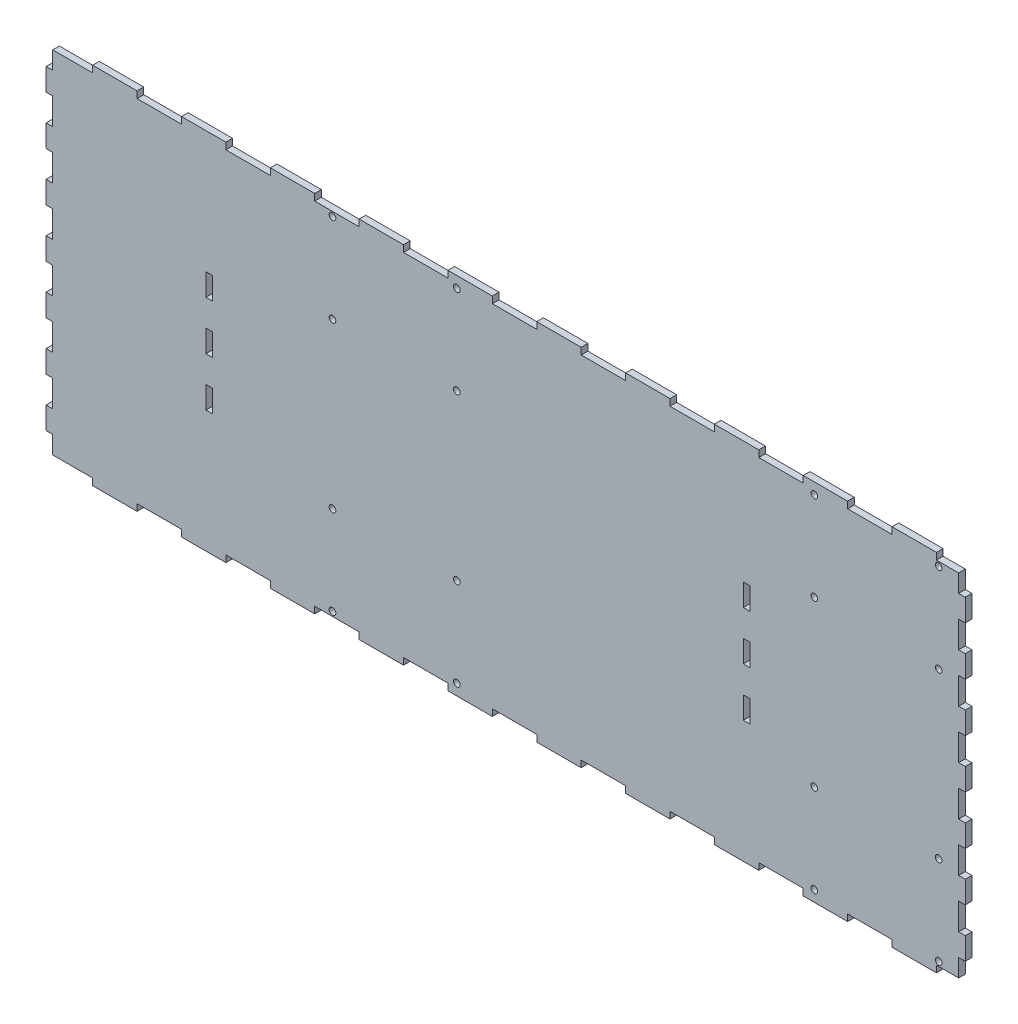
SolidWorks part; units mm, degrees
material "birch 3mm plywood"
ref_plane "Front Plane" through (0, 0, 0) normal (0, 0, 1) x (1, 0, 0)
ref_plane "Top Plane" through (0, 0, 0) normal (0, 1, 0) x (1, 0, 0)
ref_plane "Right Plane" through (0, 0, 0) normal (1, 0, 0) x (0, 0, -1)
sketch "Sketch1" plane through (0, 0, 152) normal (0, 0, 1) x (1, 0, 0)
  line L1 (-207, 82) -> (207, 82)
  line L2 (-207, 82) -> (-207, -82)
  line L3 (-207, -82) -> (207, -82)
  line L4 (207, 82) -> (207, -82)
  line L12 (200, -75) -> (-200, -75) construction
  line L13 (200, 75) -> (200, -75) construction
  line L14 (-200, -75) -> (-200, 75) construction
  line L15 (-200, 75) -> (200, 75) construction
  line L26 (-200, 0) -> (200, 0) construction
  line L31 (-200, 0) -> (200, 0) construction
  point P14 (0, 0)
  point P15 (0, 0)
  point P32 (-47.5, -25.9413)
  point P35 (256.981, -145.9413)
  point P38 (10.8894, 25.9413)
  point P51 (10.8894, -25.9413)
  point P54 (256.981, 145.9413)
  dimension "D1" = 7
  dimension "D2" = 7
  dimension "D3" = 7
  dimension "D4" = 7
  dimension "D5" = 150
  dimension "D6" = 400
extrude "Boss-Extrude1" add sketch "Sketch1" along normal blind 3
sketch "Sketch2" plane through (-207, 0, 0) normal (-1, 0, 0) x (0, 0, 1)
  line L7 (155, -82) -> (152, -82)
  line L8 (152, -82) -> (152, -71)
  line L9 (152, 82) -> (155, 82)
  line L10 (155, 82) -> (155, 71)
  line L11 (152, -61) -> (152, -49)
  line L12 (155, -71) -> (155, -82)
  line L13 (155, -49) -> (155, -61)
  line L14 (152, -39) -> (152, -27)
  line L15 (152, -17) -> (152, -5)
  line L16 (155, -27) -> (155, -39)
  line L17 (155, -5) -> (155, -17)
  line L18 (152, 5) -> (152, 17)
  line L19 (152, 27) -> (152, 39)
  line L20 (155, 17) -> (155, 5)
  line L21 (155, 39) -> (155, 27)
  line L22 (152, 49) -> (152, 61)
  line L23 (152, 71) -> (152, 82)
  line L24 (155, 61) -> (155, 49)
  line L76 (132.5, 88.6) -> (132.5, 93.6)
  line L77 (132.5, 88.6) -> (132.5, 93.6)
  line L78 (129.5, 98.6) -> (128.8771, 98.6)
  line L79 (129.5, 98.6) -> (128.8771, 98.6)
  line L80 (129.5, 82) -> (129.5, 88.6)
  line L81 (129.5, 82) -> (129.5, 88.6)
  line L82 (129.5, 88.6) -> (132.5, 88.6)
  line L83 (129.5, 88.6) -> (132.5, 88.6)
  line L85 (16, 82) -> (16, -82)
  line L102 (129.5, -82) -> (133, -82)
  line L103 (133, -82) -> (133, -79)
  line L104 (133, -79) -> (145, -79)
  line L105 (145, -79) -> (145, -82)
  line L106 (145, -82) -> (155, -82)
  line L107 (155, -82) -> (155, -71)
  line L108 (155, -71) -> (152, -71)
  line L109 (152, -71) -> (152, -61)
  line L110 (152, -61) -> (155, -61)
  line L111 (155, -61) -> (155, -49)
  line L112 (155, -49) -> (152, -49)
  line L113 (152, -49) -> (152, -39)
  line L114 (152, -39) -> (155, -39)
  line L115 (155, -39) -> (155, -27)
  line L116 (155, -27) -> (152, -27)
  line L117 (152, -27) -> (152, -17)
  line L118 (152, -17) -> (155, -17)
  line L119 (155, -17) -> (155, -5)
  line L120 (155, -5) -> (152, -5)
  line L121 (152, -5) -> (152, 5)
  line L122 (152, 5) -> (155, 5)
  line L123 (155, 5) -> (155, 17)
  line L124 (155, 17) -> (152, 17)
  line L125 (152, 17) -> (152, 27)
  line L126 (152, 27) -> (155, 27)
  line L127 (155, 27) -> (155, 39)
  line L128 (155, 39) -> (152, 39)
  line L129 (152, 39) -> (152, 49)
  line L130 (152, 49) -> (155, 49)
  line L131 (155, 49) -> (155, 61)
  line L132 (155, 61) -> (152, 61)
  line L133 (152, 61) -> (152, 71)
  line L134 (152, 71) -> (155, 71)
  line L135 (155, 71) -> (155, 82)
  line L136 (155, 82) -> (145, 82)
  line L137 (145, 82) -> (145, 79)
  line L138 (145, 79) -> (133, 79)
  line L139 (133, 79) -> (133, 82)
  line L140 (133, 82) -> (129.5, 82)
  line L184 (155, -71) -> (152, -71)
  line L186 (152, -61) -> (155, -61)
  line L188 (155, -49) -> (152, -49)
  line L190 (152, -39) -> (155, -39)
  line L192 (155, -27) -> (152, -27)
  line L194 (152, -17) -> (155, -17)
  line L196 (155, -5) -> (152, -5)
  line L198 (152, 5) -> (155, 5)
  line L200 (155, 17) -> (152, 17)
  line L202 (152, 27) -> (155, 27)
  line L204 (155, 39) -> (152, 39)
  line L206 (152, 49) -> (155, 49)
  line L208 (155, 61) -> (152, 61)
  line L210 (152, 71) -> (155, 71)
  line L297 (132.5, 93.6) -> (129.5, 93.6)
  line L298 (132.5, 93.6) -> (129.5, 93.6)
  line L299 (129.5, 93.6) -> (129.5, 98.6)
  line L300 (129.5, 93.6) -> (129.5, 98.6)
  line L301 (128.8771, -98.6) -> (129.5, -98.6)
  line L302 (128.8771, -98.6) -> (129.5, -98.6)
  line L303 (129.5, -98.6) -> (129.5, -93.6)
  line L304 (129.5, -98.6) -> (129.5, -93.6)
  line L305 (129.5, -93.6) -> (132.5, -93.6)
  line L306 (129.5, -93.6) -> (132.5, -93.6)
  line L307 (132.5, -93.6) -> (132.5, -88.6)
  line L308 (132.5, -93.6) -> (132.5, -88.6)
  line L309 (132.5, -88.6) -> (129.5, -88.6)
  line L310 (132.5, -88.6) -> (129.5, -88.6)
  line L311 (129.5, -88.6) -> (129.5, -82)
  line L312 (129.5, -88.6) -> (129.5, -82)
  arc A4 (128.8771, 98.6) -> (16, 82) centre (128.8771, -293.4723) ccw
  arc A5 (128.8771, 98.6) -> (16, 82) centre (128.8771, -293.4723) ccw
  arc A6 (16, -82) -> (128.8771, -98.6) centre (128.8771, 293.4723) ccw
  arc A7 (16, -82) -> (128.8771, -98.6) centre (128.8771, 293.4723) ccw
  line M77 (152, 82) -> (152, -82)
  line M78 (152, -82) -> (155, -82)
  line M79 (155, -82) -> (155, 82)
  line M80 (155, 82) -> (152, 82)
  dimension "D1" = 0
extrude "Cut-Extrude1" cut sketch "Sketch2" against normal blind 3 contours L184 M79 M77 M78 | L188 L186 M79 M77 | L192 L190 M79 M77 | L196 L194 M79 M77 | L200 L198 M79 M77 | L204 L202 M79 M77 | L208 L206 M79 M77 | L210 M77 M79 M80 region at (-207, -76.5, 153.5) region at (-207, -55, 153.5) region at (-207, -33, 153.5) region at (-207, -11, 153.5) region at (-207, 11, 153.5) region at (-207, 33, 153.5) region at (-207, 55, 153.5) region at (-207, 76.5, 153.5)
mirror "Mirror1" about plane through (0, 0, 0) normal (1, 0, 0) of "Cut-Extrude1"
sketch "Sketch3" plane through (0, 82, 0) normal (0, 1, 0) x (1, 0, 0)
  line L92 (174, -152) -> (194, -152)
  line L93 (194, -152) -> (194, -155)
  line L94 (194, -155) -> (204, -155)
  line L97 (207, -45) -> (204, -45)
  line L120 (204, -16) -> (-204, -16)
  line L123 (-204, -45) -> (-207, -45)
  line L146 (-204, -155) -> (-186, -155)
  line L147 (-186, -155) -> (-186, -152)
  line L148 (-186, -152) -> (-166, -152)
  line L149 (-166, -152) -> (-166, -155)
  line L150 (-166, -155) -> (-146, -155)
  line L151 (-146, -155) -> (-146, -152)
  line L152 (-146, -152) -> (-126, -152)
  line L153 (-126, -152) -> (-126, -155)
  line L154 (-126, -155) -> (-106, -155)
  line L155 (-106, -155) -> (-106, -152)
  line L156 (-106, -152) -> (-86, -152)
  line L157 (-86, -152) -> (-86, -155)
  line L158 (-86, -155) -> (-66, -155)
  line L159 (-66, -155) -> (-66, -152)
  line L160 (-66, -152) -> (-46, -152)
  line L161 (-46, -152) -> (-46, -155)
  line L162 (-46, -155) -> (-26, -155)
  line L163 (-26, -155) -> (-26, -152)
  line L164 (-26, -152) -> (-6, -152)
  line L165 (-6, -152) -> (-6, -155)
  line L166 (-6, -155) -> (14, -155)
  line L167 (14, -155) -> (14, -152)
  line L168 (14, -152) -> (34, -152)
  line L169 (34, -152) -> (34, -155)
  line L170 (34, -155) -> (54, -155)
  line L171 (54, -155) -> (54, -152)
  line L172 (54, -152) -> (74, -152)
  line L173 (74, -152) -> (74, -155)
  line L174 (74, -155) -> (94, -155)
  line L175 (94, -155) -> (94, -152)
  line L176 (94, -152) -> (114, -152)
  line L177 (114, -152) -> (114, -155)
  line L178 (114, -155) -> (134, -155)
  line L179 (134, -155) -> (134, -152)
  line L180 (134, -152) -> (154, -152)
  line L181 (154, -152) -> (154, -155)
  line L182 (154, -155) -> (174, -155)
  line L183 (174, -155) -> (174, -152)
  line L184 (174, -152) -> (194, -152)
  line L185 (194, -152) -> (194, -155)
  line L186 (194, -155) -> (204, -155)
  line L212 (204, -16) -> (-204, -16)
  line L238 (-204, -155) -> (-186, -155)
  line L239 (-186, -155) -> (-186, -152)
  line L240 (-186, -152) -> (-166, -152)
  line L241 (-166, -152) -> (-166, -155)
  line L242 (-166, -155) -> (-146, -155)
  line L243 (-146, -155) -> (-146, -152)
  line L244 (-146, -152) -> (-126, -152)
  line L245 (-126, -152) -> (-126, -155)
  line L246 (-126, -155) -> (-106, -155)
  line L247 (-106, -155) -> (-106, -152)
  line L248 (-106, -152) -> (-86, -152)
  line L249 (-86, -152) -> (-86, -155)
  line L250 (-86, -155) -> (-66, -155)
  line L251 (-66, -155) -> (-66, -152)
  line L252 (-66, -152) -> (-46, -152)
  line L253 (-46, -152) -> (-46, -155)
  line L254 (-46, -155) -> (-26, -155)
  line L255 (-26, -155) -> (-26, -152)
  line L256 (-26, -152) -> (-6, -152)
  line L257 (-6, -152) -> (-6, -155)
  line L258 (-6, -155) -> (14, -155)
  line L259 (14, -155) -> (14, -152)
  line L260 (14, -152) -> (34, -152)
  line L261 (34, -152) -> (34, -155)
  line L262 (34, -155) -> (54, -155)
  line L263 (54, -155) -> (54, -152)
  line L264 (54, -152) -> (74, -152)
  line L265 (74, -152) -> (74, -155)
  line L266 (74, -155) -> (94, -155)
  line L267 (94, -155) -> (94, -152)
  line L268 (94, -152) -> (114, -152)
  line L269 (114, -152) -> (114, -155)
  line L270 (114, -155) -> (134, -155)
  line L271 (134, -155) -> (134, -152)
  line L272 (134, -152) -> (154, -152)
  line L273 (154, -152) -> (154, -155)
  line L274 (154, -155) -> (174, -155)
  line L275 (174, -155) -> (174, -152)
  line L576 (-204, -45) -> (-207, -45)
  line L577 (-207, -45) -> (-207, -57)
  line L578 (-207, -45) -> (-207, -57)
  line L579 (-207, -57) -> (-204, -57)
  line L580 (-207, -57) -> (-204, -57)
  line L581 (-204, -57) -> (-204, -67)
  line L582 (-204, -57) -> (-204, -67)
  line L583 (-204, -67) -> (-207, -67)
  line L584 (-204, -67) -> (-207, -67)
  line L585 (-207, -67) -> (-207, -79)
  line L586 (-207, -67) -> (-207, -79)
  line L587 (-207, -79) -> (-204, -79)
  line L588 (-207, -79) -> (-204, -79)
  line L589 (-204, -79) -> (-204, -89)
  line L590 (-204, -79) -> (-204, -89)
  line L591 (-204, -89) -> (-207, -89)
  line L592 (-204, -89) -> (-207, -89)
  line L593 (-207, -89) -> (-207, -101)
  line L594 (-207, -89) -> (-207, -101)
  line L595 (-207, -101) -> (-204, -101)
  line L596 (-207, -101) -> (-204, -101)
  line L597 (-204, -101) -> (-204, -111)
  line L598 (-204, -101) -> (-204, -111)
  line L599 (-204, -111) -> (-207, -111)
  line L600 (-204, -111) -> (-207, -111)
  line L601 (-207, -111) -> (-207, -123)
  line L602 (-207, -111) -> (-207, -123)
  line L603 (-207, -123) -> (-204, -123)
  line L604 (-207, -123) -> (-204, -123)
  line L605 (-204, -123) -> (-204, -133)
  line L606 (-204, -123) -> (-204, -133)
  line L607 (-204, -133) -> (-207, -133)
  line L608 (-204, -133) -> (-207, -133)
  line L609 (-207, -133) -> (-207, -145)
  line L610 (-207, -133) -> (-207, -145)
  line L611 (-207, -145) -> (-204, -145)
  line L612 (-207, -145) -> (-204, -145)
  line L613 (-204, -145) -> (-204, -155)
  line L614 (-204, -145) -> (-204, -155)
  line L615 (-204, -16) -> (-204, -23)
  line L616 (-204, -16) -> (-204, -23)
  line L617 (-204, -23) -> (-207, -23)
  line L618 (-204, -23) -> (-207, -23)
  line L619 (-207, -23) -> (-207, -35)
  line L620 (-207, -23) -> (-207, -35)
  line L621 (-207, -35) -> (-204, -35)
  line L622 (-207, -35) -> (-204, -35)
  line L623 (-204, -35) -> (-204, -45)
  line L624 (-204, -35) -> (-204, -45)
  line L741 (207, -45) -> (204, -45)
  line L742 (204, -45) -> (204, -35)
  line L743 (204, -45) -> (204, -35)
  line L744 (204, -35) -> (207, -35)
  line L745 (204, -35) -> (207, -35)
  line L746 (207, -35) -> (207, -23)
  line L747 (207, -35) -> (207, -23)
  line L748 (207, -23) -> (204, -23)
  line L749 (207, -23) -> (204, -23)
  line L750 (204, -23) -> (204, -16)
  line L751 (204, -23) -> (204, -16)
  line L752 (204, -155) -> (204, -145)
  line L753 (204, -155) -> (204, -145)
  line L754 (204, -145) -> (207, -145)
  line L755 (204, -145) -> (207, -145)
  line L756 (207, -145) -> (207, -133)
  line L757 (207, -145) -> (207, -133)
  line L758 (207, -133) -> (204, -133)
  line L759 (207, -133) -> (204, -133)
  line L760 (204, -133) -> (204, -123)
  line L761 (204, -133) -> (204, -123)
  line L762 (204, -123) -> (207, -123)
  line L763 (204, -123) -> (207, -123)
  line L764 (207, -123) -> (207, -111)
  line L765 (207, -123) -> (207, -111)
  line L766 (207, -111) -> (204, -111)
  line L767 (207, -111) -> (204, -111)
  line L768 (204, -111) -> (204, -101)
  line L769 (204, -111) -> (204, -101)
  line L770 (204, -101) -> (207, -101)
  line L771 (204, -101) -> (207, -101)
  line L772 (207, -101) -> (207, -89)
  line L773 (207, -101) -> (207, -89)
  line L774 (207, -89) -> (204, -89)
  line L775 (207, -89) -> (204, -89)
  line L776 (204, -89) -> (204, -79)
  line L777 (204, -89) -> (204, -79)
  line L778 (204, -79) -> (207, -79)
  line L779 (204, -79) -> (207, -79)
  line L780 (207, -79) -> (207, -67)
  line L781 (207, -79) -> (207, -67)
  line L782 (207, -67) -> (204, -67)
  line L783 (207, -67) -> (204, -67)
  line L784 (204, -67) -> (204, -57)
  line L785 (204, -67) -> (204, -57)
  line L786 (204, -57) -> (207, -57)
  line L787 (204, -57) -> (207, -57)
  line L788 (207, -57) -> (207, -45)
  line L789 (207, -57) -> (207, -45)
  dimension "D1" = 0
extrude "Cut-Extrude2" cut sketch "Sketch3" against normal blind 3
mirror "Mirror2" about plane through (0, 0, 0) normal (0, 1, 0) of "Cut-Extrude2"
sketch "Sketch4" plane through (0, 0, 155) normal (0, 0, 1) x (1, 0, 0)
  line L0 (-132, 27) -> (-132, 17) construction
  line L1 (-132, 17) -> (-135, 17) construction
  line L2 (-135, 17) -> (-135, 27) construction
  line L3 (-135, 27) -> (-132, 27) construction
  line L4 (-132, 5) -> (-132, -5) construction
  line L5 (-132, -5) -> (-135, -5) construction
  line L6 (-135, -5) -> (-135, 5) construction
  line L7 (-135, 5) -> (-132, 5) construction
  line L8 (-132, -17) -> (-132, -27) construction
  line L9 (-132, -27) -> (-135, -27) construction
  line L10 (-135, -27) -> (-135, -17) construction
  line L11 (-135, -17) -> (-132, -17) construction
  line L12 (-132, 27) -> (-132, 17)
  line L13 (-132, 17) -> (-135, 17)
  line L14 (-135, 17) -> (-135, 27)
  line L15 (-135, 27) -> (-132, 27)
  line L16 (-132, 5) -> (-132, -5)
  line L17 (-132, -5) -> (-135, -5)
  line L18 (-135, -5) -> (-135, 5)
  line L19 (-135, 5) -> (-132, 5)
  line L20 (-132, -17) -> (-132, -27)
  line L21 (-132, -27) -> (-135, -27)
  line L22 (-135, -27) -> (-135, -17)
  line L23 (-135, -17) -> (-132, -17)
  line L24 (110, 27) -> (110, 17) construction
  line L25 (110, 17) -> (107, 17) construction
  line L26 (107, 17) -> (107, 27) construction
  line L27 (107, 27) -> (110, 27) construction
  line L28 (110, 5) -> (110, -5) construction
  line L29 (110, -5) -> (107, -5) construction
  line L30 (107, -5) -> (107, 5) construction
  line L31 (107, 5) -> (110, 5) construction
  line L32 (110, -17) -> (110, -27) construction
  line L33 (110, -27) -> (107, -27) construction
  line L34 (107, -27) -> (107, -17) construction
  line L35 (107, -17) -> (110, -17) construction
  line L36 (110, 27) -> (110, 17)
  line L37 (110, 17) -> (107, 17)
  line L38 (107, 17) -> (107, 27)
  line L39 (107, 27) -> (110, 27)
  line L40 (110, 5) -> (110, -5)
  line L41 (110, -5) -> (107, -5)
  line L42 (107, -5) -> (107, 5)
  line L43 (107, 5) -> (110, 5)
  line L44 (110, -17) -> (110, -27)
  line L45 (110, -27) -> (107, -27)
  line L46 (107, -27) -> (107, -17)
  line L47 (107, -17) -> (110, -17)
  line L80 (207, 0) -> (-207, 0) construction
  line L81 (207, -5) -> (207, 5) construction
  line L82 (-207, 5) -> (-207, -5) construction
  circle A0 centre (139, 37) radius 1.5 construction
  circle A1 centre (195, 37) radius 1.5 construction
  circle A2 centre (195, 77) radius 1.5 construction
  circle A3 centre (139, 77) radius 1.5 construction
  circle A4 centre (-78, 77) radius 1.5 construction
  circle A5 centre (-22, 77) radius 1.5 construction
  circle A6 centre (-78, 37) radius 1.5 construction
  circle A7 centre (-22, 37) radius 1.5 construction
  circle A8 centre (139, 37) radius 1.5
  circle A9 centre (195, 37) radius 1.5
  circle A10 centre (195, 77) radius 1.5
  circle A11 centre (139, 77) radius 1.5
  circle A12 centre (-78, 77) radius 1.5
  circle A13 centre (-22, 77) radius 1.5
  circle A14 centre (-78, 37) radius 1.5
  circle A15 centre (-22, 37) radius 1.5
  circle A16 centre (139, -77) radius 1.5
  circle A17 centre (195, -77) radius 1.5
  circle A18 centre (195, -37) radius 1.5
  circle A19 centre (139, -37) radius 1.5
  circle A20 centre (-22, -37) radius 1.5
  circle A21 centre (-78, -37) radius 1.5
  circle A22 centre (-22, -77) radius 1.5
  circle A23 centre (-78, -77) radius 1.5
extrude "Cut-Extrude3" cut sketch "Sketch4" against normal blind 10
